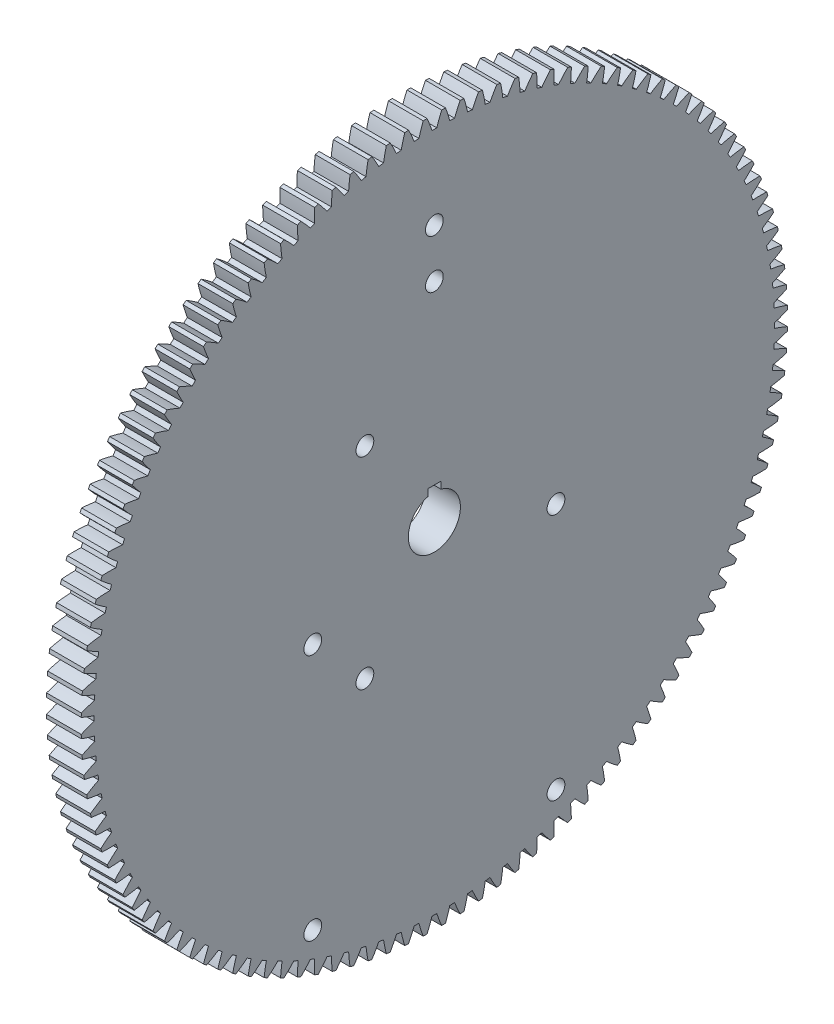
SolidWorks part; units mm, degrees
ref_plane "Plane1" through (0, 0, 0) normal (0, 0, 1) x (1, 0, 0)
ref_plane "Plane2" through (0, 0, 0) normal (0, 1, 0) x (1, 0, 0)
ref_plane "Plane3" through (0, 0, 0) normal (1, 0, 0) x (0, 0, -1)
other "Configuration Table"
sketch "HoldingSke" plane through (0, 0, 0) normal (0, 1, 0) x (1, 0, 0)
  line L0 (0, 0) -> (-152.4, -263.9645)
  line L1 (-15, 0) -> (100, 0) construction
  line L2 (0, 0) -> (-2.1039, 2.3779)
  line L3 (0, 0) -> (-11.863, 4.5341)
  line L4 (0, 0) -> (-4.318, 7.479)
  line L5 (0, 0) -> (-47.5972, -17.7524)
  line L6 (0, 0) -> (-10.5278, -7.1032)
  line L7 (-2.1039, 2.3779) -> (8.8308, 51.9871)
  line L8 (-76.2, 54.61) -> (-54.9402, 54.61)
  line L9 (-71.009, 38.7566) -> (-53.1078, 45.2721)
  line L10 (-76.2, 71.12) -> (104.1128, 71.12)
  line L11 (0, 0) -> (-12.7, 0)
  line L12 (-76.2, 101.6) -> (-76.1147, 101.6)
  line L13 (24.9733, 27.94) -> (52.9518, 28.4284)
  line L14 (24.9733, 27.94) -> (24.9746, 27.94)
  line L15 (24.9733, 27.94) -> (100.4006, 29.5858)
  circle A0 centre (0, 0) radius 9.525
  circle A1 centre (0, 0) radius 38.1
  circle A2 centre (0, 0) radius 38.1
  circle A3 centre (0, 0) radius 9.525
  dimension "Num_teeth" = 120
  dimension "H" = 19.05
  dimension "Pitch_radius" = 180.3128
  dimension "Width" = 12.7
  dimension "Thickness" = 12.7
sketch "BasProSke" plane through (0, 0, 0) normal (0, 1, 0) x (1, 0, 0)
  line L0 (-10, 0) -> (60, 0) construction
  line L1 (0, 0) -> (0, 129.1167)
  line L2 (0, 0) -> (12.7, 0)
  line L3 (12.7, 0) -> (12.7, 129.1167)
  line L4 (12.7, 129.1167) -> (0, 129.1167)
  dimension "Thickness" = 12.7
  dimension "Diameter" = 258.2333
revolve "Base-Revolve" add sketch "BasProSke" angle 360 about L0
sketch "TooCutSke" plane through (0, 0, 0) normal (1, 0, 0) x (0, 0, -1)
  line L1 (0, 0) -> (0, 107) construction
  line L2 (0, 0) -> (-1.8117, 126.9871) construction
  line L3 (0, 0) -> (-6.6485, 253.8949) construction
  line L4 (-1.8117, 126.9871) -> (-3.3242, 126.9475) construction
  arc A0 (0.878, 124.3498) -> (-0.878, 124.3498) centre (0, 0) ccw
  arc A1 (2.6872, 129.1141) -> (-2.6872, 129.1141) centre (0, 0) ccw
  circle A2 centre (0, 0) radius 127 construction
  circle A3 centre (0, 0) radius 119.341 construction
  arc A4 (-0.878, 124.3498) -> (-2.6872, 129.1141) centre (-49.2141, 108.7209) ccw
  arc A5 (2.6872, 129.1141) -> (0.878, 124.3498) centre (49.2141, 108.7209) ccw
extrude "ToothCut" cut sketch "TooCutSke" along normal through all
fillet "Breaks" [suppressed] radius 0.0423 tangent propagation no
fillet "RootFillets" [suppressed] radius 0.5304
pattern_circular "TeethCuts" count 120 every 3 about axis through (-10, 0, 0) along (1, 0, 0) of "ToothCut", "RootFillets", "Breaks"
sketch "HubNeaOneSke" plane through (0, 0, 0) normal (-1, 0, 0) x (0, 0, 1)
  circle A0 centre (0, 0) radius 38.1
  dimension "Diameter" = 76.2
extrude "HubNearOne" [suppressed] add sketch "HubNeaOneSke" along normal blind 38.1001
sketch "HubNeaBotSke" plane through (0, 0, 0) normal (-1, 0, 0) x (0, 0, 1)
  circle A0 centre (0, 0) radius 38.1
  dimension "Diameter" = 76.2
extrude "HubNearBoth" [suppressed] add sketch "HubNeaBotSke" along normal blind 19.05
ref_plane "FarPln" through (12.7, 0, 0) normal (1, 0, 0) x (0, 0, -1)
sketch "HubFarSke" plane through (12.7, 0, 0) normal (1, 0, 0) x (0, 0, -1)
  circle A0 centre (0, 0) radius 38.1
  dimension "Diameter" = 76.2
extrude "HubFar" [suppressed] add sketch "HubFarSke" along normal blind 19.05
sketch "BorSke" plane through (0, 0, 0) normal (1, 0, 0) x (0, 0, -1)
  circle A0 centre (0, 0) radius 9.525
  dimension "Diameter" = 19.05
extrude "Bore" cut sketch "BorSke" along normal mid plane 101.6001
sketch "KeySke" plane through (0, 0, 0) normal (1, 0, 0) x (0, 0, -1)
  line L0 (-2.3813, 0) -> (-2.3813, 11.7348)
  line L1 (-2.3813, 11.7348) -> (2.3813, 11.7348)
  line L2 (2.3813, 11.7348) -> (2.3813, 0)
  line L3 (0, 0) -> (0, 34) construction
  line L4 (-2.3813, 0) -> (2.3813, 0)
  dimension "Width" = 4.7625
extrude "Keyway" cut sketch "KeySke" along normal mid plane 101.6001
pattern_circular "Keyway2" [suppressed] count 2 every 90 about axis through (-10, 0, 0) along (1, 0, 0)
sketch "Sketch1" plane through (0, 0, 0) normal (-1, 0, 0) x (0, 0, 1)
  line L0 (0, 0) -> (46.9612, 0) construction
  line L1 (0, 0) -> (0, -76.4863) construction
  circle A2 centre (25.4, 36.83) radius 3.2512
  circle A3 centre (25.4, -36.83) radius 3.2512
  circle A4 centre (0, 93.98) radius 3.2512
  circle A5 centre (0, 76.2) radius 3.2512
  circle A6 centre (44.45, -16.51) radius 3.2512
  circle A7 centre (44.45, -106.934) radius 3.2512
  circle A8 centre (-44.45, -106.934) radius 3.2512
  circle A9 centre (-44.45, -16.51) radius 3.2512
  dimension "D1" = 6.5024
  dimension "D2" = 6.5024
  dimension "D6" = 6.5024
  dimension "D7" = 6.5024
  dimension "D10" = 6.5024
  dimension "D11" = 6.5024
  dimension "D3" = 17.78
  dimension "D4" = 73.66
  dimension "D5" = 25.4
  dimension "D8" = 76.2
  dimension "D9" = 73.66
  dimension "D12" = 90.424
  dimension "D13" = 44.45
  dimension "D14" = 16.51
extrude "Cut-Extrude1" cut sketch "Sketch1" against normal through all
equation "' \"Pitch@HoldingSke\" = 4"
equation "' \"Num_teeth@HoldingSke\" = 12"
equation "' \"Ap@HoldingSke\" =  20"
equation "' \"Ap@HoldingSke\" = 20"
equation "' \"Width@HoldingSke\" = 0.5"
equation "' \"Hub_dia@HoldingSke\"= 1"
equation "' \"Hub_dia@HoldingSke\" = 1"
equation "' \"Overall_len@HoldingSke\" = 1.0"
equation "' \"Bore@HoldingSke\" = 0.75"
equation "' \"T_dim@HoldingSke\" = 0.85"
equation "' \"Width@KeySke\" = 0.25"
equation "' \"Show_teeth@HoldingSke\" = 13"
equation "' \"Backlash@HoldingSke\" = 0.009"
equation "' \"Addendum_fac@HoldingSke\" = 1.0"
equation "' \"Dedendum_fac@HoldingSke\" = 1.25"
equation "' \"Dedendum_add@HoldingSke\" = 0.00005"
equation "' \"Clearance_fac@HoldingSke\" = 0.25"
equation "' \"Pitch@HoldingSke\" = 0.5"
equation "' \"Num_teeth@HoldingSke\" = 23"
equation "' \"Show_teeth@HoldingSke\" = 23"
equation "' \"Backlash@HoldingSke\" = 0.0375"
equation "\"Overcut_dia@TooCutSke\" = (\"Num_teeth@HoldingSke\" + 2 * \"Addendum_fac@HoldingSke\") / \"Pitch@HoldingSke\" + 0.002"
equation "\"Pitch_dia@TooCutSke\" = \"Num_teeth@HoldingSke\" / \"Pitch@HoldingSke\""
equation "\"Base_dia@TooCutSke\" = \"Num_teeth@HoldingSke\" / \"Pitch@HoldingSke\" * cos((\"Ap@HoldingSke\"  * 3.14159265 / 180))"
equation "\"Root_dia@TooCutSke\" = (\"Num_teeth@HoldingSke\" + 2) / \"Pitch@HoldingSke\" - 2 * (\"Addendum_fac@HoldingSke\" + \"Dedendum_fac@HoldingSke\") / \"Pitch@HoldingSke\" - \"Dedendum_add@HoldingSke\" * 2"
equation "\"Half_ang@TooCutSke\" = 180 / \"Num_teeth@HoldingSke\""
equation "\"Half_CT@TooCutSke\" = \"Num_teeth@HoldingSke\" / \"Pitch@HoldingSke\" * sin((3.14159265 / 2 / \"Num_teeth@HoldingSke\")) / 2 - 7 * \"Backlash@HoldingSke\" / 4"
equation "\"Flank_rad@TooCutSke\" = \"Num_teeth@HoldingSke\" / \"Pitch@HoldingSke\" / 5"
equation "\"Radius@RootFillets\" = \"Clearance_fac@HoldingSke\" / \"Pitch@HoldingSke\" + \"Dedendum_add@HoldingSke\""
equation "\"Break_rad@Breaks\" = 0.02 / \"Pitch@HoldingSke\""
equation "\"Thickness@HoldingSke\" = \"Width@HoldingSke\""
equation "\"OAL@HoldingSke\" = \"Thickness@HoldingSke\""
equation "\"MHD@HoldingSke\" = (\"Num_teeth@HoldingSke\" + 2) / \"Pitch@HoldingSke\" - 2 * (\"Addendum_fac@HoldingSke\" + \"Dedendum_fac@HoldingSke\")  / \"Pitch@HoldingSke\" - \"Dedendum_add@HoldingSke\" * 2"
equation "\"MBD@HoldingSke\" = (\"Num_teeth@HoldingSke\" + 2) / \"Pitch@HoldingSke\" - 2 * (\"Addendum_fac@HoldingSke\" + \"Dedendum_fac@HoldingSke\")  / \"Pitch@HoldingSke\" - \"Dedendum_add@HoldingSke\" * 2 - 0.002"
equation "\"MHD@HoldingSke\" = ((sgn( \"MHD@HoldingSke\" - \"Hub_dia@HoldingSke\" )-1)*( \"MHD@HoldingSke\" - \"Hub_dia@HoldingSke\" ))/-2+ \"Hub_dia@HoldingSke\""
equation "\"MBD@HoldingSke\" = ((sgn( \"MBD@HoldingSke\" - \"Bore@HoldingSke\" )-1)*( \"MBD@HoldingSke\" - \"Bore@HoldingSke\" ))/-2+ \"Bore@HoldingSke\""
equation "\"OAL@HoldingSke\" = ((sgn( \"OAL@HoldingSke\" - \"Overall_len@HoldingSke\" )+1)*( \"OAL@HoldingSke\" - \"Overall_len@HoldingSke\" ))/2 + \"Overall_len@HoldingSke\" + 0.000002"
equation "\"Num_teeth@TeethCuts\" = int( \"Show_teeth@HoldingSke\" ) + 1"
equation "\"Num_teeth@TeethCuts\" = ((sgn( \"Num_teeth@TeethCuts\" - \"Num_teeth@HoldingSke\" )-1)*( \"Num_teeth@TeethCuts\" - \"Num_teeth@HoldingSke\" ))/-2+ \"Num_teeth@HoldingSke\""
equation "\"Num_teeth@TeethCuts\" = ((sgn( \"Num_teeth@TeethCuts\" - 2.0)+1)*( \"Num_teeth@TeethCuts\" - 2.0))/2 +2.0"
equation "\"Angle@TeethCuts\" = 360.0 / \"Num_teeth@HoldingSke\""
equation "\"Diameter@BasProSke\" = (\"Num_teeth@HoldingSke\" + 2 * \"Addendum_fac@HoldingSke\") / \"Pitch@HoldingSke\""
equation "\"Thickness@BasProSke\"  = \"Thickness@HoldingSke\""
equation "' \"Fillet_rad@BasProSke\" =  \"Thickness@HoldingSke\" * 0.05"
equation "' \"Fillet_rad@BasProSke\" = \"Thickness@HoldingSke\" * 0.05"
equation "\"MHD@HoldingSke\" = ((sgn( \"MHD@HoldingSke\" - \"Root_dia@TooCutSke\" )-1)*( \"MHD@HoldingSke\" - \"Root_dia@TooCutSke\" ))/-2+ \"Root_dia@TooCutSke\""
equation "\"Diameter@HubNeaOneSke\" = \"MHD@HoldingSke\""
equation "\"Length@HubNearOne\" = \"OAL@HoldingSke\" - \"Thickness@BasProSke\""
equation "\"Diameter@HubNeaBotSke\" = \"MHD@HoldingSke\""
equation "\"Length@HubNearBoth\" = ( \"OAL@HoldingSke\" - \"Thickness@BasProSke\" ) / 2.0"
equation "\"Thickness@FarPln\" = \"Thickness@BasProSke\""
equation "\"Diameter@HubFarSke\" = \"MHD@HoldingSke\""
equation "\"Length@HubFar\" = ( \"OAL@HoldingSke\" - \"Thickness@BasProSke\" ) / 2.0"
equation "\"Diameter@BorSke\" = \"MBD@HoldingSke\""
equation "\"D1@Bore\" = \"OAL@HoldingSke\" * 2.0"
equation "\"D1@Keyway\" = \"OAL@HoldingSke\" * 2.0"
equation "\"Offset@KeySke\" = \"T_dim@HoldingSke\" - \"MBD@HoldingSke\" / 2.0"
